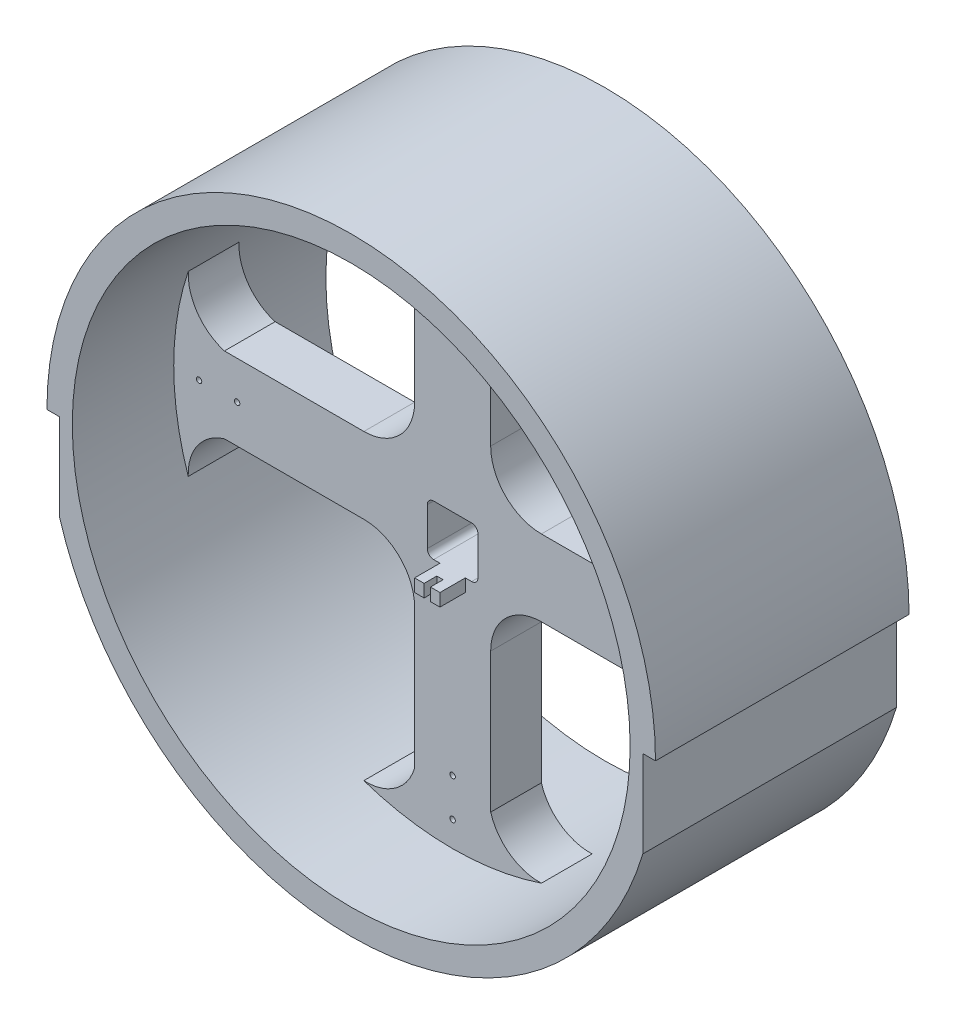
SolidWorks part; units mm, degrees
material "6061 Alloy"
ref_plane "Front Plane" through (0, 0, 0) normal (0, 0, 1) x (1, 0, 0)
ref_plane "Top Plane" through (0, 0, 0) normal (0, 1, 0) x (1, 0, 0)
ref_plane "Right Plane" through (0, 0, 0) normal (1, 0, 0) x (0, 0, -1)
sketch "Sketch1" plane through (0, 0, 0) normal (0, 0, 1) x (1, 0, 0)
  circle A0 centre (0, 0) radius 152.4
  circle A1 centre (0, 0) radius 139.7
  dimension "D1" = 304.8
  dimension "D2" = 279.4
extrude "Boss-Extrude1" add sketch "Sketch1" along normal mid plane 127
sketch "Sketch2" plane through (0, 0, 0) normal (0, 0, 1) x (1, 0, 0)
  line L0 (-114.3, 19.05) -> (-138.7192, 19.05)
  line L1 (-147.1918, -19.05) -> (147.1918, -19.05)
  line L2 (-147.1918, -19.05) -> (-147.1918, 19.05)
  line L3 (-147.1918, 19.05) -> (147.1918, 19.05)
  line L4 (147.1918, -19.05) -> (147.1918, 19.05)
  line L5 (-147.1918, -19.05) -> (147.1918, 19.05) construction
  line L6 (-147.1918, 19.05) -> (147.1918, -19.05) construction
  line L7 (19.05, -143.9568) -> (-19.05, -143.9568)
  line L8 (19.05, -143.9568) -> (19.05, 143.9568)
  line L9 (19.05, 143.9568) -> (-19.05, 143.9568)
  line L10 (-19.05, -143.9568) -> (-19.05, 143.9568)
  line L11 (19.05, -143.9568) -> (-19.05, 143.9568) construction
  line L12 (19.05, 143.9568) -> (-19.05, -143.9568) construction
  line L15 (-44.45, 19.05) -> (-19.05, 19.05)
  line L16 (-19.05, 44.45) -> (-19.05, 19.05)
  line L17 (-132.4254, 44.4927) -> (-143.3503, 19.05)
  line L18 (-143.3503, 19.05) -> (-138.7192, 19.05)
  line L19 (-138.7192, 19.05) -> (-143.3503, 19.05)
  line L20 (-19.05, 114.3) -> (-19.05, 143.9568)
  line L21 (-44.45, 132.4398) -> (-19.05, 143.9568)
  line L22 (44.45, 19.05) -> (19.05, 19.05)
  line L23 (19.05, 44.45) -> (19.05, 19.05)
  line L24 (19.05, 143.3503) -> (19.05, 138.7192)
  line L25 (19.05, 114.3) -> (19.05, 138.7192)
  line L26 (44.4927, 132.4254) -> (19.05, 143.3503)
  line L27 (114.3, 19.05) -> (143.9568, 19.05)
  line L28 (132.4398, 44.45) -> (143.9568, 19.05)
  line L29 (19.05, -44.45) -> (19.05, -19.05)
  line L30 (44.45, -19.05) -> (19.05, -19.05)
  line L31 (143.3503, -19.05) -> (138.7192, -19.05)
  line L32 (114.3, -19.05) -> (138.7192, -19.05)
  line L33 (132.4254, -44.4927) -> (143.3503, -19.05)
  line L34 (19.05, -114.3) -> (19.05, -143.9568)
  line L35 (44.45, -132.4398) -> (19.05, -143.9568)
  line L36 (-44.45, -19.05) -> (-19.05, -19.05)
  line L37 (-19.05, -44.45) -> (-19.05, -19.05)
  line L38 (-19.05, -143.3503) -> (-19.05, -138.7192)
  line L39 (-19.05, -114.3) -> (-19.05, -138.7192)
  line L40 (-44.4927, -132.4254) -> (-19.05, -143.3503)
  line L41 (-114.3, -19.05) -> (-143.9568, -19.05)
  line L42 (-132.4398, -44.45) -> (-143.9568, -19.05)
  arc A1 (-44.45, 19.05) -> (-19.05, 44.45) centre (-44.45, 44.45) ccw
  arc A2 (-114.3, 19.05) -> (-132.4254, 44.4927) centre (-107.0492, 43.3931) cw
  circle A3 centre (0, 0) radius 139.7 construction
  arc A5 (-19.05, 114.3) -> (-44.45, 132.4398) centre (-43.3968, 107.0616) ccw
  arc A6 (19.05, 44.45) -> (44.45, 19.05) centre (44.45, 44.45) ccw
  arc A7 (19.05, 114.3) -> (44.4927, 132.4254) centre (43.3931, 107.0492) cw
  arc A8 (114.3, 19.05) -> (132.4398, 44.45) centre (107.0616, 43.3968) ccw
  arc A9 (44.45, -19.05) -> (19.05, -44.45) centre (44.45, -44.45) ccw
  arc A10 (114.3, -19.05) -> (132.4254, -44.4927) centre (107.0492, -43.3931) cw
  arc A11 (19.05, -114.3) -> (44.45, -132.4398) centre (43.3968, -107.0616) ccw
  arc A12 (-19.05, -44.45) -> (-44.45, -19.05) centre (-44.45, -44.45) ccw
  arc A13 (-19.05, -114.3) -> (-44.4927, -132.4254) centre (-43.3931, -107.0492) cw
  arc A14 (-114.3, -19.05) -> (-132.4398, -44.45) centre (-107.0616, -43.3968) ccw
  point P0 (0, 0)
  point P6 (0, 0)
  point P67 (0, 0)
  dimension "D3" = 25.4
  dimension "D5" = 25.4
  dimension "D1" = 38.1
  dimension "D2" = 38.1
  dimension "D4" = 114.3
  dimension "D6" = 114.3
  dimension "D7" = 4
extrude "Boss-Extrude2" add sketch "Sketch2" along normal mid plane 25.4 contours L1 L10 L3 L2 | L10 L1 L8 L3 | L10 L3 L8 L9 | L8 L1 L4 L3 | L10 L7 L8 L1 | A14 L1 L42 | L10 A13 L40 | A11 L8 L35 | A9 L1 L8 | L1 A10 L33 | A8 L3 L28 | L8 A7 L26 | A5 L10 L21 | L0 A2 L17 L3 | A1 L3 L10 | A6 L8 L3 | A12 L10 L1 region at (-83.1209, 0, 0) region at (-132.2215, 26.1932, 0) region at (-24.7235, 24.7235, 0) region at (0, 81.5034, 0) region at (0, 0, 0) region at (24.7235, 24.7235, 0) region at (83.1209, 0, 0) region at (-24.7235, -24.7235, 0) region at (0, -81.5034, 0) region at (-26.2233, 132.4495, 0) region at (24.7235, -24.7235, 0) region at (-132.4495, -26.2233, 0) region at (132.4495, 26.2233, 0) region at (26.1932, 132.2215, 0) region at (-26.1932, -132.2215, 0) region at (132.2215, -26.1932, 0) region at (26.2233, -132.4495, 0)
sketch "Sketch4" plane through (0, 0, 0) normal (0, 0, 1) x (1, 0, 0)
  line L0 (-12.7, -19.05) -> (-12.7, 6.35)
  line L5 (-12.7, -19.05) -> (12.7, -19.05)
  line L6 (-12.7, 6.35) -> (12.7, 6.35)
  line L7 (12.7, -19.05) -> (12.7, 6.35)
  line L8 (-12.7, -19.05) -> (12.7, 6.35) construction
  line L9 (-12.7, 6.35) -> (12.7, -19.05) construction
  point P0 (-5.6792, -9.9337)
  point P1 (0, -6.35)
  dimension "D1" = 25.4
  dimension "D2" = 25.4
  dimension "D3" = 0
  dimension "D4" = 6.35
extrude "Cut-Extrude3" cut sketch "Sketch4" against normal through all both and the other way through all
sketch "Sketch8" plane through (0, 0, 63.5) normal (0, 0, 1) x (1, 0, 0)
  line L0 (-146.05, 0) -> (-163.2527, 0)
  line L1 (-146.05, 0) -> (-146.05, -50.8)
  line L2 (-163.2527, 0) -> (-163.2527, -50.8)
  line L3 (-146.05, -50.8) -> (-163.2527, -50.8)
  circle A0 centre (0, 0) radius 152.4 construction
  dimension "D1" = 50.8
  dimension "D2" = 146.05
extrude "Cut-Extrude5" cut sketch "Sketch8" against normal through all
mirror "Mirror1" about plane through (0, 0, 0) normal (1, 0, 0) of "Cut-Extrude5"
hole_wizard "#4-40 Tapped Hole1" positions "Sketch11" profile "Sketch12" tap size "#4-40" standard "ANSI Inch" end condition through all
sketch "Sketch11" plane through (0, 0, 12.7) normal (0, 0, 1) x (1, 0, 0)
  line L0 (-19.05, 44.45) -> (-19.05, 114.3) construction
  line L1 (44.45, 19.05) -> (114.3, 19.05) construction
  point P0 (-14.2875, 88.9)
  point P2 (-6.0325, 88.9)
  point P4 (88.9, 14.2875)
  point P6 (88.9, 6.0325)
  dimension "D1" = 88.9
  dimension "D2" = 88.9
  dimension "D3" = 8.255
  dimension "D4" = 8.255
  dimension "D5" = 88.9
  dimension "D6" = 4.7625
  dimension "D7" = 4.7625
sketch "Sketch12" plane through (-14.2875, 88.9, 12.7) normal (1, 0, 0) x (0, -1, 0)
  line L0 (0, 0) -> (0, 76.2)
  line L1 (0, 76.2) -> (1.1303, 76.2)
  line L2 (1.1303, 76.2) -> (1.1303, 0)
  line L5 (1.1303, 0) -> (0, 0)
  line L11 (0, -6.35) -> (0, 107.95) construction
  dimension "Thru Tap Drill Dia." = 2.2606
  dimension "Thru Tap Drill Depth" = 76.2
cosmetic thread "Hole Thread1" parameters "D2"=2.8448
cosmetic thread "Hole Thread2" parameters "D2"=2.8448
cosmetic thread "Hole Thread3" parameters "D2"=2.8448
cosmetic thread "Hole Thread4" parameters "D2"=2.8448
hole_wizard "#6-32 Tapped Hole1" positions "Sketch13" profile "Sketch14" tap size "#6-32" standard "ANSI Inch" end condition through all
sketch "Sketch13" plane through (0, 0, 12.7) normal (0, 0, 1) x (1, 0, 0)
  point P0 (-107.95, 0)
  point P2 (-127, 0)
  dimension "D1" = 107.95
  dimension "D2" = 19.05
sketch "Sketch14" plane through (-107.95, 0, 12.7) normal (1, 0, 0) x (0, -1, 0)
  line L0 (0, 0) -> (0, 76.2)
  line L1 (0, 76.2) -> (1.3525, 76.2)
  line L2 (1.3525, 76.2) -> (1.3525, 0)
  line L5 (1.3525, 0) -> (0, 0)
  line L11 (0, -6.35) -> (0, 107.95) construction
  dimension "Thru Tap Drill Dia." = 2.7051
  dimension "Thru Tap Drill Depth" = 76.2
cosmetic thread "Hole Thread5" parameters "D2"=3.5052
cosmetic thread "Hole Thread6" parameters "D2"=3.5052
pattern_circular "CirPattern1" count 4 every 90 about axis through (0, 0, 63.5) along (0, 0, 1) of "#6-32 Tapped Hole1"
sketch "Sketch17" plane through (0, 0, 12.7) normal (0, 0, 1) x (1, 0, 0)
  line L0 (-12.7, -19.05) -> (12.7, -19.05) construction
  line L1 (-12.7, 6.35) -> (-12.7, -19.05) construction
  line L2 (-12.7, -15.875) -> (-12.7, -19.05)
  line L3 (-12.7, -19.05) -> (-9.525, -19.05)
  line L4 (12.7, 6.35) -> (-12.7, 6.35) construction
  line L5 (12.7, -19.05) -> (12.7, 6.35) construction
  line L6 (-12.7, 3.175) -> (-12.7, 6.35)
  line L7 (-12.7, 6.35) -> (-9.525, 6.35)
  line L8 (9.525, 6.35) -> (12.7, 6.35)
  line L9 (12.7, 6.35) -> (12.7, 3.175)
  line L10 (12.7, -15.875) -> (12.7, -19.05)
  line L11 (12.7, -19.05) -> (9.525, -19.05)
  arc A0 (-9.525, -19.05) -> (-12.7, -15.875) centre (-9.525, -15.875) cw
  arc A1 (-12.7, 3.175) -> (-9.525, 6.35) centre (-9.525, 3.175) cw
  arc A2 (9.525, 6.35) -> (12.7, 3.175) centre (9.525, 3.175) cw
  arc A3 (9.525, -19.05) -> (12.7, -15.875) centre (9.525, -15.875) ccw
  dimension "D1" = 3.175
  dimension "D4" = 3.175
  dimension "D5" = 3.175
  dimension "D6" = 3.175
  dimension "D12" = 3.175
  dimension "D2" = 3.175
  dimension "D3" = 3.175
  dimension "D7" = 3.175
  dimension "D8" = 3.175
  dimension "D9" = 3.175
  dimension "D10" = 3.175
  dimension "D11" = 3.175
extrude "Boss-Extrude4" add sketch "Sketch17" against normal up to surface (25.4 mm away) up to face at (1.3525, 107.95, -12.7)
sketch "Sketch18" plane through (0, 0, 12.7) normal (0, 0, 1) x (1, 0, 0)
  line L0 (-9.525, -19.05) -> (9.525, -19.05) construction
  line L1 (-6.35, -19.05) -> (6.35, -19.05)
  line L2 (-6.35, -19.05) -> (-6.35, -25.4)
  line L3 (-6.35, -25.4) -> (6.35, -25.4)
  line L4 (6.35, -19.05) -> (6.35, -25.4)
  line L5 (-12.7, 3.175) -> (-12.7, -15.875) construction
  dimension "D1" = 12.7
  dimension "D2" = 6.35
  dimension "D3" = 6.35
extrude "Boss-Extrude5" add sketch "Sketch18" along normal blind 12.7 and the other way blind 38.1
sketch "Sketch19" plane through (0, -19.05, 0) normal (0, 1, 0) x (1, 0, 0)
  line L0 (6.35, -25.4) -> (-6.35, -25.4) construction
  line L1 (-1.5875, -25.4) -> (1.5875, -25.4)
  line L2 (-1.5875, -25.4) -> (-1.5875, -19.05)
  line L3 (-1.5875, -19.05) -> (1.5875, -19.05)
  line L4 (1.5875, -25.4) -> (1.5875, -19.05)
  line L5 (-6.35, -12.7) -> (-6.35, -25.4) construction
  dimension "D1" = 3.175
  dimension "D2" = 4.7625
  dimension "D3" = 6.35
extrude "Cut-Extrude6" cut sketch "Sketch19" against normal up to next
sketch "Sketch20" plane through (0, -19.05, 0) normal (0, 1, 0) x (1, 0, 0)
  line L0 (6.35, 25.4) -> (-6.35, 25.4) construction
  line L1 (1.5875, 25.4) -> (-1.5875, 25.4)
  line L2 (1.5875, 25.4) -> (1.5875, 19.05)
  line L3 (1.5875, 19.05) -> (-1.5875, 19.05)
  line L4 (-1.5875, 25.4) -> (-1.5875, 19.05)
  line L5 (6.35, 25.4) -> (6.35, 12.7) construction
  dimension "D1" = 3.175
  dimension "D2" = 6.35
  dimension "D3" = 4.7625
extrude "Cut-Extrude7" cut sketch "Sketch20" against normal up to next
